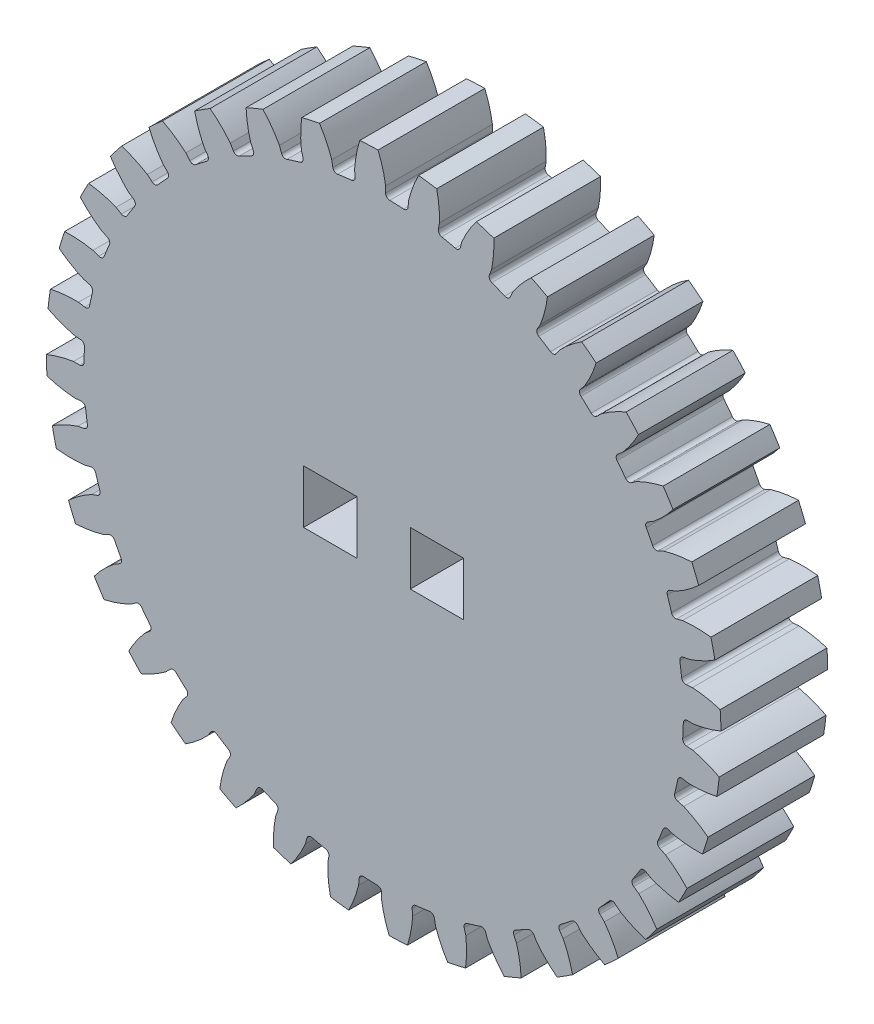
SolidWorks part; units mm, degrees
ref_plane "Front" through (0, 0, 0) normal (0, 0, 1) x (1, 0, 0)
ref_plane "Top" through (0, 0, 0) normal (0, 1, 0) x (1, 0, 0)
ref_plane "Right" through (0, 0, 0) normal (1, 0, 0) x (0, 0, -1)
sketch "Sketch1" plane through (0, 0, 0) normal (0, 0, 1) x (1, 0, 0)
  line L0 (-457.2, 0) -> (457.2, 0) construction
  circle A0 centre (0, 0) radius 20.066
  circle A1 centre (0, 0) radius 19.05 construction
  circle A3 centre (0, 0) radius 17.8255 construction
  dimension "D1" = 1.2245
  dimension "D2" = 2.2405
  dimension "D3" = 1.016
extrude "Boss-Extrude1" add sketch "Sketch1" against normal blind 6.35
sketch "Sketch2" plane through (0, 0, 0) normal (1, 0, 0) x (0, 0, -1)
  line L0 (6.35, 0) -> (15.875, 0)
  line L1 (6.35, 0) -> (6.35, 14.2875)
  line L2 (6.35, 14.2875) -> (15.875, 14.2875)
  line L3 (15.875, 14.2875) -> (15.875, 0)
  point P5 (15.875, -14.2875)
  dimension "Face Wd" = 6.35
  dimension "B Hub Dia" = 28.575
  dimension "D O'all Lg." = 15.875
sketch "Sketch3" plane through (0, 0, 0) normal (0, 0, 1) x (1, 0, 0)
  line L0 (0, 0) -> (0, 20.066) construction
  line L1 (-4.6178, 17.8558) -> (0, 19.05)
  line L2 (-9.5921, 19.05) -> (9.5921, 19.05) construction
  line L3 (-9.2865, 16.6483) -> (9.2865, 21.4517) construction
  line L4 (-4.6178, 17.8558) -> (0, 0) construction
  line L5 (-11.4075, 14.4921) -> (0, 0) construction
  line L6 (-11.4075, 14.4921) -> (-1.663, 22.1626) construction
  line L7 (-3.22, 18.16) -> (0, 0) construction
  line L8 (-3.22, 18.16) -> (0.0676, 18.7429) construction
  arc A0 (-4.6178, 17.8558) -> (-11.4075, 14.4921) centre (0, 0) ccw
  circle A1 centre (0, 0) radius 19.05 construction
  circle A2 centre (0, 0) radius 18.4432 construction
  arc A3 (-4.6178, 17.8558) -> (-3.22, 18.16) centre (0, 0) cw
  circle A4 centre (0, 0) radius 20.066 construction
  point P6 (0, 19.05)
  dimension "D1" = 4.7697
  dimension "Pressure Angle" = 14.5
  dimension "D2" = 7.6316
  dimension "D3" = 12.4013
  dimension "D4" = 1.4309
  dimension "D5" = 3.3388
sketch "Sketch4" plane through (0, 0, 0) normal (0, 0, 1) x (1, 0, 0)
  line L0 (0, 0) -> (0.8302, 19.0138) construction
  line L1 (0.1199, 18.4428) -> (0.1199, 17.8251)
  line L2 (0, 19.05) -> (1.6603, 18.9775) construction
  line L3 (1.488, 18.3831) -> (1.4342, 17.7677)
  line L4 (0.1199, 17.8251) -> (0, 0) construction
  line L5 (0, 0) -> (0, 20.066) construction
  arc A0 (1.4342, 17.7677) -> (0.1199, 17.8251) centre (0, 0) ccw
  arc A1 (0, 19.05) -> (1.6603, 18.9775) centre (0, 0) cw construction
  circle A2 centre (0, 0) radius 19.05 construction
  circle A3 centre (0, 0) radius 18.4432 construction
  circle A4 centre (0, 0) radius 17.8255 construction
  arc A5 (3.5883, 21.9333) -> (-1.663, 22.1626) centre (0, 0) ccw
  spline S0 degree 2 poles (-1.663, 22.1626) (-0.1927, 20.4949) (0.1199, 18.4428) knots 0 0 0 1 1 1
  spline S1 degree 2 poles (3.5883, 21.9333) (1.9782, 20.4001) (1.488, 18.3831) knots 0 0 0 1 1 1
  dimension "D1" = 1.6624
extrude "Cut-Extrude1" cut sketch "Sketch4" against normal through all
fillet "Fillet1" radius 0.2494 2 edges at (1.4342, 17.7677, -3.175) (0.1199, 17.8251, -3.175)
pattern_circular "CirPattern1" count 36 over 360 about axis through (0, 0, -6.35) along (0, 0, 1) of "Cut-Extrude1", "Fillet1"
sketch "Sketch5" plane through (0, 0, 0) normal (0, 0, 1) x (1, 0, 0)
  circle A0 centre (0, 0) radius 6.35
  circle A1 centre (0, 0) radius 7.9375 construction
  dimension "Bore Min" = 12.7
  dimension "Bore Max" = 15.875
sketch "Pitch Dia" plane through (0, 0, 0) normal (0, 0, 1) x (1, 0, 0)
  circle A0 centre (0, 0) radius 19.05 construction
  circle A1 centre (0, 0) radius 19.05
sketch "Sketch6" plane through (0, 0, 0) normal (0, 0, 1) x (1, 0, 0)
  line L0 (-1.5875, 0) -> (1.5875, 0) construction
  line L1 (1.5875, 1.5875) -> (4.7625, 1.5875)
  line L2 (1.5875, 1.5875) -> (1.5875, -1.5875)
  line L3 (1.5875, -1.5875) -> (4.7625, -1.5875)
  line L4 (4.7625, 1.5875) -> (4.7625, -1.5875)
  line L5 (-4.7625, 1.5875) -> (-1.5875, 1.5875)
  line L6 (-4.7625, 1.5875) -> (-4.7625, -1.5875)
  line L7 (-4.7625, -1.5875) -> (-1.5875, -1.5875)
  line L8 (-1.5875, 1.5875) -> (-1.5875, -1.5875)
  point P8 (-1.5875, 0)
  point P9 (1.5875, 0)
  point P13 (0, 0)
  dimension "D1" = 3.175
  dimension "D2" = 3.175
extrude "Cut-Extrude2" cut sketch "Sketch6" against normal through all both and the other way through all
equation "\"D1@Boss-Extrude1\"=.25in"
equation "\"D1@Sketch4\" = 1.5708/(\"Number of Teeth@Sketch1\"/\"Ptich Dia@Sketch1\")"
equation "\"D1@CirPattern1\" = \"Number of Teeth@Sketch1\""
equation "\"D1@Fillet1\" = \"D1@Sketch4\"*.15"
equation "\"D1@Sketch1\" = 1.157/(\"Number of Teeth@Sketch1\"/\"Ptich Dia@Sketch1\")"
